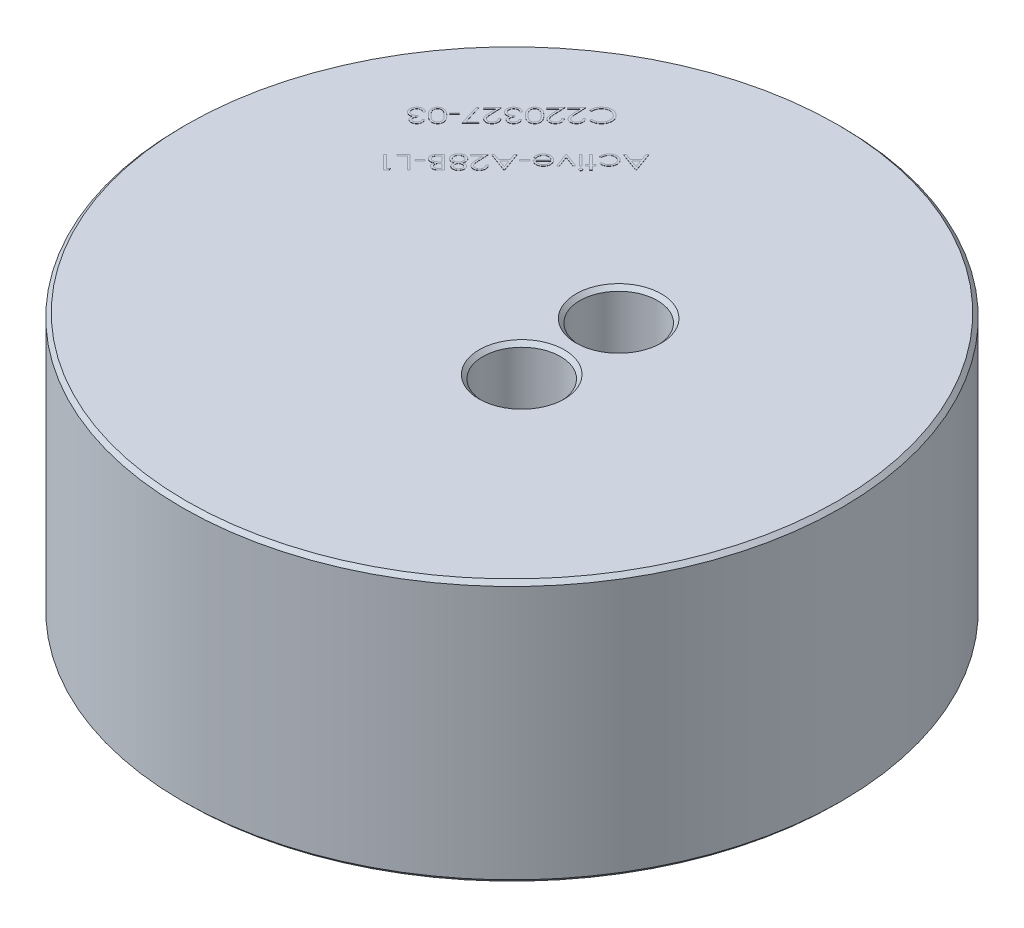
SolidWorks part; units mm, degrees
material "6061-T6 (SS)"
ref_plane "Front Plane" through (0, 0, 0) normal (0, 0, 1) x (1, 0, 0)
ref_plane "Top Plane" through (0, 0, 0) normal (0, 1, 0) x (1, 0, 0)
ref_plane "Right Plane" through (0, 0, 0) normal (1, 0, 0) x (0, 0, -1)
ref_axis "CentralAxis" through (0, 16.5607, 0) along (0, -1, 0)
sketch "BaseS" plane through (0, 0, 0) normal (0, 1, 0) x (1, 0, 0)
  circle A0 centre (0, 0) radius 17
  dimension "Diameter" = 34
extrude "Base" add sketch "BaseS" along normal mid plane 13.5
sketch "HoleS" plane through (0, 6.75, 0) normal (0, 1, 0) x (1, 0, 0)
  line L0 (3, 2.5) -> (3, -2.5) construction
  line L1 (0, 0) -> (3, 0) construction
  circle A0 centre (3, 2.5) radius 2
  dimension "Diameter" = 4
  dimension "Spacing" = 5
  dimension "XDim" = 3
extrude "Hole" cut sketch "HoleS" against normal through all
mirror "HoleVM" about plane through (0, 0, 0) normal (0, 0, 1) of "Hole"
sketch "TextS" plane through (0, 6.75, 0) normal (0, 1, 0) x (1, 0, 0)
  line L0 (-1.4142, 12.7279) -> (-12.7279, 1.4142) construction
  line L1 (0, 0) -> (-7.0711, 7.0711) construction
  line L2 (0, 0) -> (0, 17) construction
  circle A0 centre (0, 0) radius 17 construction
  text T0 "Active-A28B-L1\r\nC220327-03" font "Century Gothic" height 1
  dimension "D1" = 16
  dimension "Angle" = 45
  dimension "YDim" = 10
extrude "Text" add sketch "TextS" along normal blind 0.01
chamfer "BaseChamfer" distance 0.2 angle 45 2 edges at (0, -6.75, 17) (0, 6.75, 17)
chamfer "HoleChamfer" distance 0.2 angle 45 2 edges at (3, 6.75, 0.5) (3, 6.75, -0.5)
